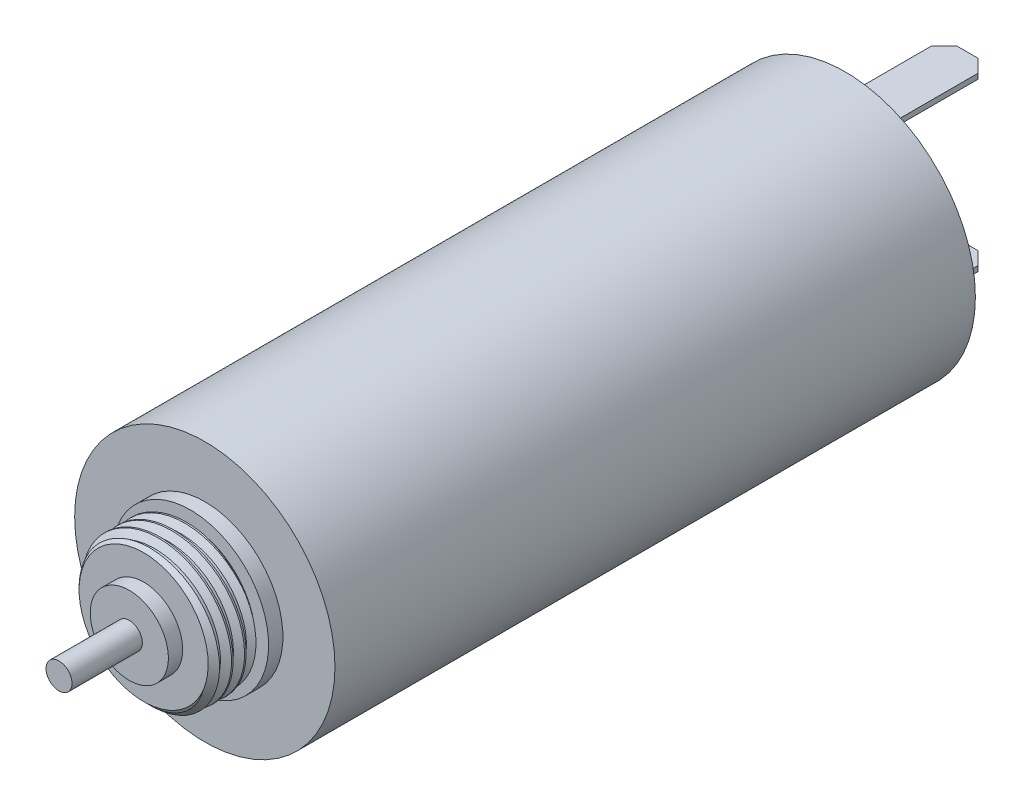
SolidWorks part; units mm, degrees
ref_plane "Front Plane" through (0, 0, 0) normal (0, 0, 1) x (1, 0, 0)
ref_plane "Top Plane" through (0, 0, 0) normal (0, 1, 0) x (1, 0, 0)
ref_plane "Right Plane" through (0, 0, 0) normal (1, 0, 0) x (0, 0, -1)
sketch "Sketch1" plane through (0, 0, 0) normal (0, 0, 1) x (1, 0, 0)
  circle A0 centre (0, 0) radius 5
  circle A1 centre (0, 0) radius 0.5
  circle A2 centre (0, 0) radius 3 construction
  circle A4 centre (0, 0) radius 1.95 construction
  circle A5 centre (0, 0) radius 2.75 construction
  circle A6 centre (0, 0) radius 1.5 construction
  point P6 (0, 5)
  point P7 (0, 0.5)
  point P8 (0, 3)
  point P9 (0, -5)
  point P10 (0, 1.95)
  point P12 (0, 2.75)
  point P14 (0, 1.5)
  dimension "D1" = 3.9
  dimension "OD" = 10
  dimension "D2" = 3
  dimension "Shaft Dia." = 1
  dimension "D3" = 6
  dimension "Thread OD" = 5.5
sketch "Sketch2" plane through (0, 0, 0) normal (1, 0, 0) x (0, 0, -1)
  line L0 (0, 0) -> (34.9, 0) construction
  point P3 (5.05, 0)
  point P4 (5.6, 0)
  point P5 (30.2, 0)
  point P6 (31.1, 0)
  point P7 (3.25, 0)
  point P8 (2.7, 0)
  dimension "D1" = 34.9
  dimension "D2" = 5.6
  dimension "D5" = 0.55
  dimension "D6" = 0.9
  dimension "D3" = 24.6
  dimension "D4" = 4.7
  dimension "D7" = 2.35
  dimension "D8" = 2.9
sketch "Sketch3" plane through (0, 0, 0) normal (1, 0, 0) x (0, 0, -1)
  line L2 (31.1, 0) -> (31.1, 1.95)
  line L3 (31.1, 1.95) -> (30.2, 1.95)
  line L4 (30.2, 1.95) -> (30.2, 5)
  line L5 (30.2, 5) -> (5.6, 5)
  line L6 (5.6, 5) -> (5.6, 3)
  line L7 (5.6, 3) -> (5.05, 3)
  line L8 (5.05, 3) -> (5.05, 2.75)
  line L9 (2.7, 0.5) -> (0, 0.5)
  line L11 (5.05, 2.75) -> (3.25, 2.75)
  line L12 (31.1, 0) -> (0, 0)
  line L13 (0, 0) -> (0, 0.5)
  line L14 (3.25, 2.75) -> (3.25, 1.5)
  line L15 (3.25, 1.5) -> (2.7, 1.5)
  line L16 (2.7, 1.5) -> (2.7, 0.5)
revolve "Revolve1" add sketch "Sketch3" angle 360 mid plane about L12
sketch "Sketch5" plane through (0, 0, -3.25) normal (0, 0, 1) x (1, 0, 0)
  circle A2 centre (0, 0) radius 2.75
  circle A3 centre (0, 0) radius 2.75
  point P3 (0, 2.75)
  dimension "D1" = 0
curve "Helix/Spiral1" pitch 0.5 height 1.8 turns 3.6 parameters "Pitch"=0.5
sketch "Sketch6" plane through (0, 0, 0) normal (1, 0, 0) x (0, 0, -1)
  line L0 (3.2812, 2.8041) -> (2.7812, 2.8041) construction
  line L1 (2.7812, 2.8041) -> (3.0312, 2.3711) construction
  line L2 (3.0312, 2.3711) -> (3.2812, 2.8041) construction
  line L3 (3.0625, 2.4252) -> (3, 2.4252) construction
  line L4 (3.25, 2.75) -> (2.8125, 2.75) construction
  line L5 (3.0312, 2.3711) -> (3.0312, 2.4252) construction
  line L6 (3.0312, 2.75) -> (3.0312, 2.8041) construction
  line L7 (3.0937, 2.4794) -> (2.9687, 2.4794)
  line L8 (2.9687, 2.4794) -> (2.7969, 2.7771)
  line L9 (2.7969, 2.7771) -> (3.2656, 2.7771)
  line L10 (3.2656, 2.7771) -> (3.0937, 2.4794)
  line L11 (3.0312, 2.4252) -> (3.0312, 2.4794) construction
  line L12 (3.0312, 2.3711) -> (3.0312, -2.75) construction
  line L13 (3.0312, -2.75) -> (3.5312, -2.75) construction
  line L14 (3.5312, -2.75) -> (4.0312, -2.75) construction
  line L15 (4.0312, -2.75) -> (4.5313, -2.75) construction
  line L16 (3.25, -2.75) -> (5.05, -2.75) construction
  point P17 (3.0312, 2.7771)
  dimension "D1" = 0.5
  dimension "D2" = 0.0625
sweep "Cut-Sweep1" cut profiles "Sketch6" path "Helix/Spiral1" align with end faces yes
sketch "Sketch7" plane through (0, 0, 0) normal (1, 0, 0) x (0, 0, -1)
  line L0 (3.25, 2.75) -> (3.25, 2.4794)
  line L1 (3.25, 2.4794) -> (3.5206, 2.75)
  line L2 (3.5206, 2.75) -> (3.25, 2.75)
  line L3 (3.25, 2.75) -> (5.05, 2.75) construction
  line L4 (5.05, 2.75) -> (4.8312, 2.75)
  line L5 (4.8312, 2.75) -> (4.9875, 2.4794)
  line L6 (5.05, 2.4794) -> (5.05, 2.75)
  line L11 (0, 0) -> (5.05, 0) construction
  line L12 (0, 0.5) -> (0, -0.5) construction
  line L13 (5.05, 3) -> (5.05, -3) construction
  line L14 (2.9687, 2.4794) -> (2.7969, 2.7771) construction
  line L16 (4.9875, 2.4794) -> (5.05, 2.4794)
  line L17 (3.0312, 2.4794) -> (3.0937, 2.4794) construction
revolve "Cut-Revolve1" cut sketch "Sketch7" angle 360 mid plane about L11
sketch "Sketch8" plane through (0, 0, -30.2) normal (0, 0, -1) x (-1, 0, 0)
  line L0 (0, 3.3) -> (0, 3.1) construction
  line L1 (-0.9, 3.3) -> (0.9, 3.3)
  line L2 (-0.9, 3.3) -> (-0.9, 3.1)
  line L3 (-0.9, 3.1) -> (0.9, 3.1)
  line L4 (0.9, 3.3) -> (0.9, 3.1)
  line L5 (-0.9, -3.1) -> (0.9, -3.1)
  line L6 (-0.9, -3.1) -> (-0.9, -3.3)
  line L7 (-0.9, -3.3) -> (0.9, -3.3)
  line L8 (0.9, -3.1) -> (0.9, -3.3)
  line L9 (0, -3.1) -> (0, -3.3) construction
  line L10 (-0.9, 3.2) -> (0.9, 3.2) construction
  line L11 (-0.9, -3.2) -> (0.9, -3.2) construction
  line L12 (0, 3.1) -> (0, -3.1) construction
  dimension "D2" = 1.8
  dimension "D3" = 6.4
  dimension "D4" = 0.2
extrude "Boss-Extrude1" add sketch "Sketch8" along normal up to vertex (4.7 mm away) up to point (0, 0, -34.9)
chamfer "Chamfer1" distance 0.5 angle 45 4 edges at (-0.9, -3.2, -34.9) (0.9, -3.2, -34.9) (0.9, 3.2, -34.9) (-0.9, 3.2, -34.9)
scale "Scale1" scale about origin uniform scaling yes scale factor 2
equation "\"D3@Helix/Spiral1\" = \"D7@Sketch2\" - \"D5@Sketch2\""
equation "\"D1@Sketch6\" = \"Pitch@Helix/Spiral1\""
equation "\"D2@Sketch6\" = \"D1@Sketch6\" / 8"
